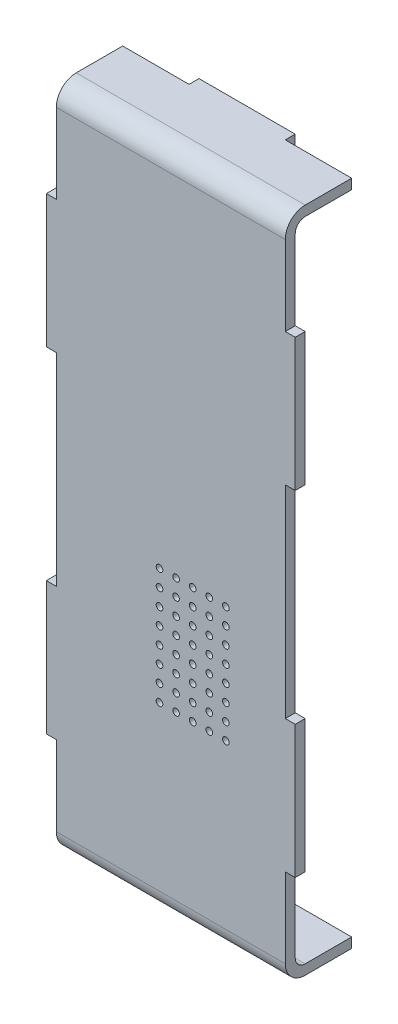
SolidWorks part; units mm, degrees
note: The reader was unsure of these and kept them because the rebuilt part matched: flange length of "边线-法兰1", "边线-法兰2".
material "ABS"
ref_plane "前视基准面" through (0, 0, 0) normal (0, 0, 1) x (1, 0, 0)
ref_plane "上视基准面" through (0, 0, 0) normal (0, 1, 0) x (1, 0, 0)
ref_plane "右视基准面" through (0, 0, 0) normal (1, 0, 0) x (0, 0, -1)
sketch "草图1" plane through (0, 0, 0) normal (0, 0, 1) x (1, 0, 0)
  line L1 (-10.4886, 92.4556) -> (64.5114, 92.4556)
  line L2 (-10.4886, 92.4556) -> (-10.4886, -99.5444)
  line L3 (-10.4886, -99.5444) -> (64.5114, -99.5444)
  line L4 (64.5114, 92.4556) -> (64.5114, -99.5444)
  dimension "D1" = 75
  dimension "D2" = 192
sheet metal parameters "钣金2" thickness 3 parameters "D1"=0
base flange "基体-法兰2" sketch "草图1" thickness 3 reverse thickness direction no parameters "D1"=0
edge flange "边线-法兰1" sketch "草图10" flange angle 90 flange length 23 flange position material outside bend radius 3 thickness 3 relief rectangular parameters "D6"=10
sketch "草图10" plane through (0, -99.5444, -3) normal (0, -1, 0) x (-1, 0, 0)
  line L0 (10.4886, 0) -> (-64.5114, 0) construction
  line L1 (10.4886, 0) -> (-64.5114, 0)
  line L2 (-64.5114, 0) -> (-64.5114, 20)
  line L3 (-64.5114, 20) -> (10.4886, 20)
  line L4 (10.4886, 20) -> (10.4886, 0)
bend "边线折弯1" bend radius 3 bend angle 90 parameters "D5"=1
edge flange "边线-法兰2" sketch "草图13" flange angle 90 flange length 23 flange position bend outside bend radius 3 thickness 3 relief rectangular parameters "D6"=10
sketch "草图13" plane through (0, 92.4556, -3) normal (0, 1, 0) x (1, 0, 0)
  line L0 (64.5114, 0) -> (-10.4886, 0) construction
  line L1 (64.5114, 0) -> (-10.4886, 0)
  line L2 (-10.4886, 0) -> (-10.4886, 20)
  line L3 (-10.4886, 20) -> (64.5114, 20)
  line L4 (64.5114, 20) -> (64.5114, 0)
bend "边线折弯2" bend radius 3 bend angle 90 parameters "D5"=2
sketch "草图18" plane through (0, 0, 0) normal (0, 0, 1) x (1, 0, 0)
  line L0 (27.0114, -102.5444) -> (27.0114, 98.4556) construction
  line L1 (64.5114, -102.5444) -> (64.5114, -72.5444)
  line L2 (64.5114, 98.4556) -> (61.5114, 98.4556)
  line L3 (64.5114, 98.4556) -> (64.5114, 68.4556)
  line L4 (64.5114, 68.4556) -> (61.5114, 68.4556)
  line L5 (-10.4886, -102.5444) -> (64.5114, -102.5444) construction
  line L6 (64.5114, 98.4556) -> (-10.4886, 98.4556) construction
  line L7 (64.5114, -2.0444) -> (-10.4886, -2.0444) construction
  line L8 (64.5114, -96.5444) -> (64.5114, 92.4556) construction
  line L9 (-10.4886, 92.4556) -> (-10.4886, -96.5444) construction
  line L10 (61.5114, 98.4556) -> (61.5114, 68.4556)
  line L12 (64.5114, -32.5444) -> (64.5114, 28.4556)
  line L13 (64.5114, 28.4556) -> (61.5114, 28.4556)
  line L14 (61.5114, -32.5444) -> (61.5114, 28.4556)
  line L15 (64.5114, -102.5444) -> (61.5114, -102.5444)
  line L16 (61.5114, -102.5444) -> (61.5114, -72.5444)
  line L17 (64.5114, -72.5444) -> (61.5114, -72.5444)
  line L18 (64.5114, -32.5444) -> (61.5114, -32.5444)
  line L19 (-10.4886, -32.5444) -> (-7.4886, -32.5444)
  line L20 (-10.4886, -72.5444) -> (-7.4886, -72.5444)
  line L21 (-7.4886, -102.5444) -> (-7.4886, -72.5444)
  line L22 (-10.4886, -102.5444) -> (-7.4886, -102.5444)
  line L23 (-7.4886, -32.5444) -> (-7.4886, 28.4556)
  line L24 (-10.4886, 28.4556) -> (-7.4886, 28.4556)
  line L25 (-10.4886, -32.5444) -> (-10.4886, 28.4556)
  line L27 (-7.4886, 98.4556) -> (-7.4886, 68.4556)
  line L28 (-10.4886, 68.4556) -> (-7.4886, 68.4556)
  line L29 (-10.4886, 98.4556) -> (-10.4886, 68.4556)
  line L30 (-10.4886, 98.4556) -> (-7.4886, 98.4556)
  line L31 (-10.4886, -102.5444) -> (-10.4886, -72.5444)
  dimension "D1" = 30
  dimension "D2" = 3
  dimension "D3" = 40
extrude "切除-拉伸1" cut sketch "草图18" against normal blind 30 normal cut yes
sketch "草图19" plane through (0, -102.5444, 0) normal (0, -1, 0) x (1, 0, 0)
  line L0 (27.0114, -23) -> (27.0114, 0) construction
  line L1 (-7.4886, -23) -> (61.5114, -23) construction
  line L2 (-7.4886, 0) -> (61.5114, 0) construction
  line L3 (12.5114, -23) -> (12.5114, -20)
  line L4 (61.5114, -23) -> (41.5114, -23)
  line L5 (61.5114, -23) -> (61.5114, -20)
  line L6 (61.5114, -20) -> (41.5114, -20)
  line L7 (41.5114, -23) -> (41.5114, -20)
  line L8 (-7.4886, -20) -> (12.5114, -20)
  line L9 (-7.4886, -23) -> (-7.4886, -20)
  line L10 (-7.4886, -23) -> (12.5114, -23)
  dimension "D1" = 3
  dimension "D2" = 20
extrude "切除-拉伸2" cut sketch "草图19" against normal blind 203 normal cut yes
sketch "草图20" plane through (0, 0, 0) normal (0, 0, 1) x (1, 0, 0)
  circle A0 centre (23.6105, -47.3103) radius 1
  circle A1 centre (28.6105, -47.3103) radius 1
  circle A2 centre (33.6105, -47.3103) radius 1
  circle A3 centre (38.6105, -47.3103) radius 1
  circle A4 centre (43.6105, -47.3103) radius 1
  circle A5 centre (28.6105, -42.3103) radius 1
  circle A6 centre (33.6105, -42.3103) radius 1
  circle A7 centre (38.6105, -42.3103) radius 1
  circle A8 centre (43.6105, -42.3103) radius 1
  circle A9 centre (28.6105, -37.3103) radius 1
  circle A10 centre (33.6105, -37.3103) radius 1
  circle A11 centre (38.6105, -37.3103) radius 1
  circle A12 centre (43.6105, -37.3103) radius 1
  circle A13 centre (28.6105, -32.3103) radius 1
  circle A14 centre (33.6105, -32.3103) radius 1
  circle A15 centre (38.6105, -32.3103) radius 1
  circle A16 centre (43.6105, -32.3103) radius 1
  circle A17 centre (28.6105, -27.3103) radius 1
  circle A18 centre (33.6105, -27.3103) radius 1
  circle A19 centre (38.6105, -27.3103) radius 1
  circle A20 centre (43.6105, -27.3103) radius 1
  circle A21 centre (28.6105, -22.3103) radius 1
  circle A22 centre (33.6105, -22.3103) radius 1
  circle A23 centre (38.6105, -22.3103) radius 1
  circle A24 centre (43.6105, -22.3103) radius 1
  circle A25 centre (28.6105, -17.3103) radius 1
  circle A26 centre (33.6105, -17.3103) radius 1
  circle A27 centre (38.6105, -17.3103) radius 1
  circle A28 centre (43.6105, -17.3103) radius 1
  circle A29 centre (28.6105, -12.3103) radius 1
  circle A30 centre (33.6105, -12.3103) radius 1
  circle A31 centre (38.6105, -12.3103) radius 1
  circle A32 centre (43.6105, -12.3103) radius 1
  circle A33 centre (23.6105, -42.3103) radius 1
  circle A34 centre (23.6105, -37.3103) radius 1
  circle A35 centre (23.6105, -32.3103) radius 1
  circle A36 centre (23.6105, -27.3103) radius 1
  circle A37 centre (23.6105, -22.3103) radius 1
  circle A38 centre (23.6105, -17.3103) radius 1
  circle A39 centre (23.6105, -12.3103) radius 1
  dimension "D1" = 5
  dimension "D2" = 8
extrude "切除-拉伸3" cut sketch "草图20" against normal blind 3 normal cut yes
unfold "展开1" [suppressed]
sketch "草图19-1" plane through (0, -97.613, 0) normal (0, 0, 1) x (1, 0, 0)
  line L0 (27.0114, -23) -> (27.0114, 0) construction
  line L3 (12.5114, -23) -> (12.5114, -20)
  line L4 (61.5114, -23) -> (41.5114, -23)
  line L5 (61.5114, -23) -> (61.5114, -20)
  line L6 (61.5114, -20) -> (41.5114, -20)
  line L7 (41.5114, -23) -> (41.5114, -20)
  line L8 (-7.4886, -20) -> (12.5114, -20)
  line L9 (-7.4886, -23) -> (-7.4886, -20)
  line L10 (-7.4886, -23) -> (12.5114, -23)
  dimension "D1" = 3
  dimension "D2" = 20
flat pattern "平板型式2"
sketch "折弯-线2" plane through (0, 0, 0) normal (0, 0, 1) x (1, 0, 0)
  line L0 (-7.4886, -100.0787) -> (61.5114, -100.0787) construction
  line L1 (-7.4886, -100.0787) -> (61.5114, -100.0787) construction
  line L2 (61.5114, 95.9899) -> (-7.4886, 95.9899) construction
  line L3 (61.5114, 95.9899) -> (-7.4886, 95.9899) construction
sketch3d "边界框2" [suppressed]
  line L0 (64.5114, 116.5242, 0) -> (64.5114, -120.613, 0) construction
  line L1 (-10.4886, 116.5242, 0) -> (-10.4886, -120.613, 0) construction
  line L2 (64.5114, 116.5242, 0) -> (-10.4886, 116.5242, 0) construction
  line L3 (64.5114, -120.613, 0) -> (-10.4886, -120.613, 0) construction
bend of the flat pattern "展开-<边线折弯1>1"
bend of the flat pattern "展开-<边线折弯2>1"
